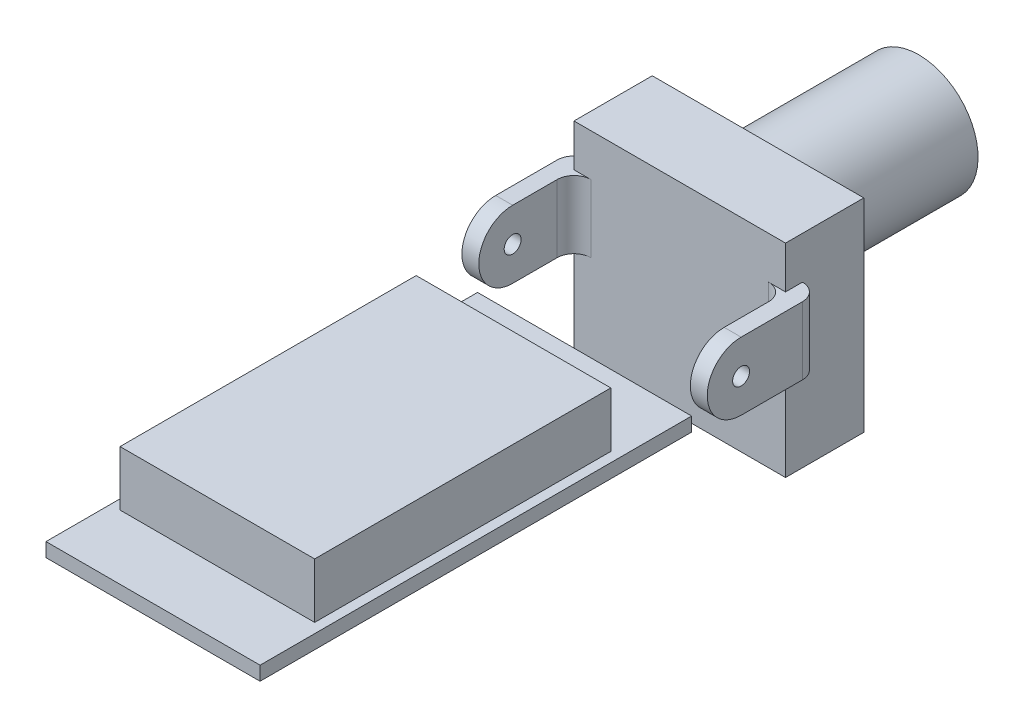
SolidWorks part; units mm, degrees
ref_plane "Front Plane" through (0, 0, 0) normal (0, 0, 1) x (1, 0, 0)
ref_plane "Top Plane" through (0, 0, 0) normal (0, 1, 0) x (1, 0, 0)
ref_plane "Right Plane" through (0, 0, 0) normal (1, 0, 0) x (0, 0, -1)
sketch "Sketch1" plane through (0, 0, 0) normal (0, 1, 0) x (1, 0, 0)
  line L1 (-12.65, -25.5) -> (12.65, -25.5)
  line L2 (-12.65, -25.5) -> (-12.65, 25.5)
  line L3 (-12.65, 25.5) -> (12.65, 25.5)
  line L4 (12.65, -25.5) -> (12.65, 25.5)
  line L5 (-12.65, -25.5) -> (12.65, 25.5) construction
  line L6 (-12.65, 25.5) -> (12.65, -25.5) construction
  point P0 (0, 0)
  dimension "D1" = 25.3
  dimension "D2" = 51
extrude "Boss-Extrude1" add sketch "Sketch1" along normal blind 1.65
sketch "Sketch2" plane through (0, 1.65, 0) normal (0, 1, 0) x (1, 0, 0)
  line L0 (12.65, 25.5) -> (-12.65, 25.5) construction
  line L1 (-11.5, -17.9) -> (11.5, -17.9)
  line L2 (-11.5, -17.9) -> (-11.5, 17.1)
  line L3 (-11.5, 17.1) -> (11.5, 17.1)
  line L4 (11.5, -17.9) -> (11.5, 17.1)
  line L5 (-11.5, -17.9) -> (11.5, 17.1) construction
  line L6 (-11.5, 17.1) -> (11.5, -17.9) construction
  point P0 (0, -0.4)
  point P6 (0, 0)
  point P9 (0.2896, -0.2296)
  point P10 (0, 0)
  point P11 (0, 0)
  point P13 (0, 0)
  dimension "D1" = 23
  dimension "D2" = 35
  dimension "D3" = 8.4
extrude "Boss-Extrude2" add sketch "Sketch2" along normal blind 6.5
sketch "Sketch3" plane through (0, 0, 0) normal (1, 0, 0) x (0, 0, -1)
  line L0 (25.5, 1.65) -> (25.5, 0) construction
  line L3 (29.5, 8.65) -> (36.75, 8.65)
  line L4 (36.75, 8.65) -> (36.75, 0.65)
  line L5 (29.5, 0.65) -> (36.75, 0.65)
  line L7 (46, 13.65) -> (46, -10.35)
  line L8 (46, 13.65) -> (36.75, 13.65)
  line L9 (36.75, 13.65) -> (36.75, -10.35)
  line L10 (46, -10.35) -> (36.75, -10.35)
  arc A0 (29.5, 8.65) -> (29.5, 0.65) centre (29.5, 4.65) ccw
  circle A1 centre (29.5, 4.65) radius 1
  dimension "D1" = 8
  dimension "D3" = 2
  dimension "D2" = 7.25
  dimension "D4" = 8
  dimension "D5" = 5
  dimension "D6" = 9.25
  dimension "D7" = 24
extrude "Boss-Extrude3" add sketch "Sketch3" along normal mid plane 25 separate body contours L10 L7 L8 L9 L4 region at (0, 1.65, -41.375)
extrude "Boss-Extrude4" add sketch "Sketch3<3>" along normal blind 2 from surface separate body contours L3 A0 L5 L4 A1 region at (0, 4.65, -31.595) starting at face at (12.5, 1.65, -41.375)
sketch "Sketch3<3>" plane through (0, 0, 0) normal (1, 0, 0) x (0, 0, -1) same geometry as "Sketch3"
extrude "Boss-Extrude5" add sketch "Sketch3<4>" against normal blind 2 from surface separate body contours L3 A0 L5 L4 A1 region at (0, 4.65, -31.595) starting at face at (-12.5, 1.65, -41.375)
sketch "Sketch3<4>" plane through (0, 0, 0) normal (1, 0, 0) x (0, 0, -1) same geometry as "Sketch3"
sketch "Sketch5" plane through (0, 0, -36.75) normal (0, 0, -1) x (1, 0, 0)
  line L1 (-14.5, -0.65) -> (14.5, -0.65)
  line L2 (-14.5, -0.65) -> (-14.5, -8.65)
  line L3 (-14.5, -8.65) -> (14.5, -8.65)
  line L4 (14.5, -0.65) -> (14.5, -8.65)
extrude "Boss-Extrude6" add sketch "Sketch5" along normal blind 2
fillet "Fillet1" radius 2 4 edges at (14.5, 4.65, -38.75) (-14.5, 4.65, -38.75) (12.5, 4.65, -36.75) (-12.5, 4.65, -36.75)
sketch "Sketch6" plane through (0, 0, -46) normal (0, 0, -1) x (1, 0, 0)
  line L0 (0, 10.35) -> (0, -13.65) construction
  line L1 (12.5, 10.35) -> (-12.5, 10.35) construction
  line L2 (12.5, -13.65) -> (-12.5, -13.65) construction
  circle A0 centre (0, -5.55) radius 7
  dimension "D1" = 14
  dimension "D2" = 8.1
extrude "Boss-Extrude7" add sketch "Sketch6" along normal blind 19
